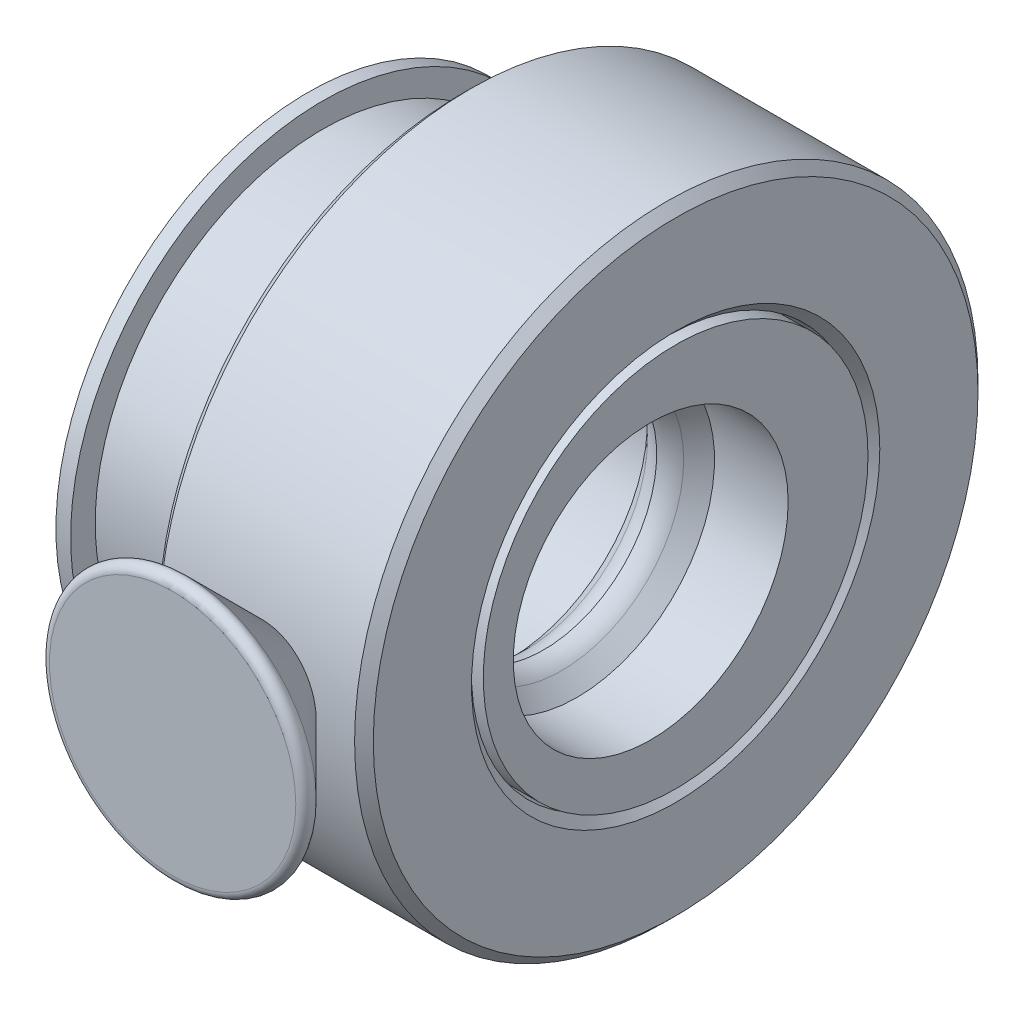
SolidWorks part; units mm, degrees
ref_plane "Front Plane" through (0, 0, 0) normal (0, 0, 1) x (1, 0, 0)
ref_plane "Top Plane" through (0, 0, 0) normal (0, 1, 0) x (1, 0, 0)
ref_plane "Right Plane" through (0, 0, 0) normal (1, 0, 0) x (0, 0, -1)
sketch "Sketch2" plane through (0, 0, 0) normal (1, 0, 0) x (0, 0, -1)
  circle A0 centre (0, 0) radius 15.875
  circle A1 centre (0, 0) radius 25.4
  dimension "D1" = 31.75
  dimension "D2" = 50.8
extrude "Boss-Extrude1" add sketch "Sketch2" along normal mid plane 17.4625
chamfer "Chamfer1" distance 0.762 angle 45 4 edges at (-8.7312, 0, -15.875) (-8.7312, 0, -25.4) (8.7312, 0, -25.4) (8.7312, 0, -15.875)
sketch "Sketch3" plane through (0, 0, 0) normal (1, 0, 0) x (0, 0, -1)
  line L0 (-13.208, 0) -> (-13.208, 3.9688)
  line L1 (-13.208, 3.9688) -> (-24.5318, 3.9687)
  line L2 (-24.5318, 3.9687) -> (-31.0847, 10.5216)
  line L3 (-32.258, 10.0356) -> (-32.258, 0)
  line L4 (-32.258, 0) -> (-13.208, 0)
  arc A0 (-31.0847, 10.5216) -> (-32.258, 10.0356) centre (-31.5707, 10.0356) ccw
  circle A1 centre (0, 0) radius 25.4 construction
  point P8 (-31.5707, 10.7229)
  point P9 (0, 0)
  point P10 (25.4, 0)
  point P11 (0, 0)
  point P19 (-25.008, 4.445)
  dimension "D2" = 1.27
  dimension "D1" = 19.05
  dimension "D3" = 4.445
  dimension "D4" = 45
  dimension "D5" = 57.658
  dimension "D6" = 3.9688
revolve "Revolve1" add sketch "Sketch3" angle 360 about L4
sketch "Sketch4" plane through (0, 0, 0) normal (1, 0, 0) x (0, 0, -1)
  circle A0 centre (-2.032, 0) radius 11.2
  circle A1 centre (0, 0) radius 15.675
  circle A2 centre (0, 0) radius 15.875 construction
  dimension "D1" = 2.032
  dimension "D2" = 22.4
  dimension "D3" = 0.2
extrude "Boss-Extrude2" add sketch "Sketch4" along normal up to surface and the other way up to surface separate body up to face at (8.7312, 0, -24.638) other way up to face at (-8.7312, 0, -16.637)
sketch "Sketch6" plane through (0, 0, 0) normal (0, 1, 0) x (1, 0, 0)
  line L0 (-2.7312, 9.168) -> (-0.7312, 7.168)
  line L1 (8.7312, 9.168) -> (-8.7312, 9.168) construction
  line L2 (-0.7312, 7.168) -> (0.7312, 7.168)
  line L3 (0.7312, 7.168) -> (2.7312, 9.168)
  line L4 (2.7312, 9.168) -> (-2.7312, 9.168)
  line L5 (-8.7312, 24.638) -> (-8.7312, -24.638) construction
  line L6 (8.7312, -24.638) -> (8.7312, 24.638) construction
  line L7 (5.0717, -2.032) -> (8.7312, -2.032) construction
  line L8 (8.7312, -13.232) -> (8.7312, 9.168) construction
  point P14 (0, 0)
  dimension "D1" = 45
  dimension "D2" = 45
  dimension "D3" = 6
  dimension "D4" = 6
  dimension "D5" = 2
revolve "Revolve2" add sketch "Sketch6" angle 360 about L7
sketch "Sketch5" plane through (0, 0, 0) normal (0, 0, 1) x (1, 0, 0)
  circle A0 centre (0, 0) radius 3.9688 construction
  circle A1 centre (0, 0) radius 3.9688
extrude "Cut-Extrude1" cut sketch "Sketch5" along normal through all
ref_axis "Axis1" through (-2.7312, 0, 2.032) along (-1, 0, 0)
sketch "Sketch8" plane through (0, 0, 0) normal (0, 1, 0) x (1, 0, 0)
  line L0 (-8.7312, 9.168) -> (-9.9453, 9.168)
  line L1 (-9.9453, 9.168) -> (-19.198, 14.51)
  line L2 (-19.198, 14.51) -> (-19.198, 18.51)
  line L3 (-19.198, 18.51) -> (-17.998, 18.51)
  line L4 (-17.998, 18.51) -> (-17.998, 16.51)
  line L5 (-17.998, 16.51) -> (-10.886, 16.51)
  line L6 (-10.886, 16.51) -> (-9.7313, 18.51)
  line L7 (-9.7313, 18.51) -> (-8.7312, 18.51)
  line L8 (-8.7312, 24.638) -> (-8.7312, -24.638) construction
  line L9 (-8.7312, 18.51) -> (-8.7312, 9.168)
  point P8 (-10.3089, 15.0897)
  point P13 (-8.7312, 17.5097)
  point P14 (-9.7313, 17.2913)
  point P15 (-12.3785, 9.168)
  point P16 (-10.886, 15.6531)
  dimension "D1" = 1.2
  dimension "D2" = 2
  dimension "D3" = 7.112
  dimension "D4" = 1
  dimension "D5" = 60
  dimension "D6" = 60
  dimension "D7" = 4
  dimension "D8" = 16.51
revolve "Revolve3" add sketch "Sketch8" angle 360 about axis through (-2.7312, 0, 2.032) along (-1, 0, 0)
fillet "Fillet1" radius 2.54 3 edges at (0.7312, 0, -7.168) (-0.7312, 0, -7.168) (-9.9453, 0, -9.168)
